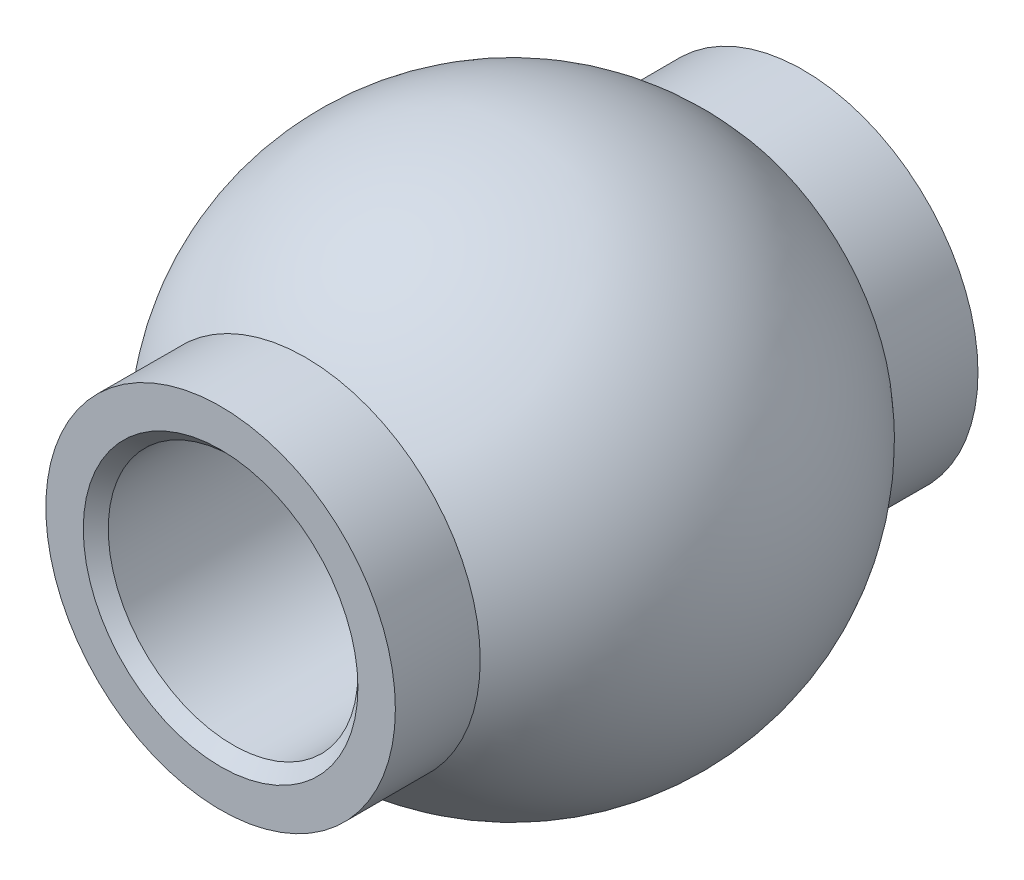
SolidWorks part; units mm, degrees
ref_plane "Front" through (0, 0, 0) normal (0, 0, 1) x (1, 0, 0)
ref_plane "Top" through (0, 0, 0) normal (0, 1, 0) x (1, 0, 0)
ref_plane "Right" through (0, 0, 0) normal (1, 0, 0) x (0, 0, -1)
sketch "Sketch1" plane through (0, 0, 0) normal (0, 0, 1) x (1, 0, 0)
  line L0 (0, 0) -> (0, -34.925)
  line L1 (0, -34.925) -> (4.7625, -34.925)
  line L2 (4.7625, -34.925) -> (4.7625, 0)
  line L3 (4.7625, 0) -> (0, 0)
  line L5 (0, 33.3375) -> (0, 0) construction
  line L6 (0, 33.3375) -> (14.2875, 33.3375) construction
  line L7 (14.2875, 33.3375) -> (14.2875, 19.05) construction
  line L8 (-4.7625, -34.925) -> (-4.7625, 0) construction
  line L9 (3.8092, -34.925) -> (4.7625, -33.9717)
  line L10 (4.8772, -34.8588) -> (4.8772, -35.918) construction
  line L11 (4.8772, -35.918) -> (3.9599, -35.3884) construction
  line L12 (3.9599, -35.3884) -> (4.8772, -34.8588) construction
  line L13 (3.9599, -35.3884) -> (4.0745, -35.3884) construction
  line L14 (4.8772, -35.3884) -> (4.7625, -35.3884) construction
  line L15 (4.0745, -35.4546) -> (4.0745, -35.3222) construction
  line L16 (4.7625, -35.8518) -> (4.7625, -34.925) construction
  line L17 (4.8198, -35.8849) -> (4.8198, -34.8919) construction
  arc A0 (8.5725, 7.62) -> (0, 33.3375) centre (0, 19.05) ccw construction
  circle A1 centre (0, 19.05) radius 4.7625 construction
  circle A2 centre (0, 19.05) radius 10.3187 construction
  circle A3 centre (0, 19.05) radius 10.8347 construction
  arc A4 (4.7625, 0) -> (8.5725, 7.62) centre (14.2875, 0) cw construction
  point P16 (-4.7625, -31.2179)
  point P28 (4.0745, -35.3884)
  point P31 (4.7625, -35.3884)
  point P34 (4.8198, -35.3884)
  dimension "Ball Dia" = 20.6375
  dimension "D1" = 21.6694
  dimension "ID" = 9.525
  dimension "D2" = 3.7071
  dimension "D3" = 45
  dimension "D4" = 0.9533
  dimension "Pitch" = 1.0592
  dimension "D5" = 0.1324
  dimension "Thread Size" = 9.525
  dimension "Overall Width" = 28.575
  dimension "Shank Thread Length" = 34.925
  dimension "Shank Center Length" = 53.975
sketch "Sketch2" plane through (0, 0, 0) normal (1, 0, 0) x (0, 0, -1)
  line L0 (-11.1125, 19.05) -> (11.1125, 19.05)
  line L2 (0, 25.7175) -> (0, 12.3825)
  line L3 (0, 23.8125) -> (0, 14.2875) construction
  line L4 (11.1125, 25.7175) -> (-11.1125, 25.7175)
  line L5 (11.1125, 23.8125) -> (-11.1125, 23.8125)
  line L6 (11.1125, 14.2875) -> (-11.1125, 14.2875)
  line L7 (11.1125, 12.3825) -> (-11.1125, 12.3825)
  line L8 (0, 19.05) -> (-11.1125, 24.8348) construction
  line L9 (0, 19.05) -> (-11.1125, 13.2652) construction
  point P0 (0, 23.8125)
  point P4 (0, 19.05)
  point P9 (0, 19.05)
  point P10 (0, 14.2875)
  point P18 (0, 23.8125)
  point P21 (0, 25.7175)
  point P24 (0, 14.2875)
  point P27 (0, 12.3825)
  dimension "D1" = 13.335
  dimension "Overall Thickness" = 22.225
  dimension "Maximum Ball Swivel" = 55
sketch "Sketch13" plane through (0, 0, 0) normal (0, 0, 1) x (1, 0, 0)
  line L0 (3.8092, -34.925) -> (4.7625, -33.9717) construction
  line L1 (3.8092, -34.925) -> (4.7625, -33.9717)
  line L4 (0, 0) -> (0, -34.925)
  line L5 (0, -34.925) -> (4.7625, -34.925)
  line L6 (4.7625, -34.925) -> (4.7625, 0)
  line L7 (4.7625, 0) -> (0, 0)
  line L8 (0, 0) -> (0, -34.925)
  line L9 (0, -34.925) -> (3.8092, -34.925)
  line L10 (4.7625, -33.9717) -> (4.7625, 0)
  line L11 (4.7625, 0) -> (0, 0)
  dimension "D1" = 0
revolve "Revolve4" [suppressed] add sketch "Sketch13" angle 360 about L8
sketch "Sketch4" plane through (0, 0, 0) normal (0, 0, 1) x (1, 0, 0)
  line L0 (4.7625, 0) -> (0, 0) construction
  line L1 (0, 8.7312) -> (0, 0)
  line L2 (0, 33.3375) -> (0, 0) construction
  line L3 (4.7625, 0) -> (0, 0)
  line L5 (0, 33.3375) -> (0, 29.3687)
  line L6 (0, 33.3375) -> (0, 35.8775) construction
  arc A0 (8.5725, 7.62) -> (0, 33.3375) centre (0, 19.05) ccw construction
  arc A1 (8.5725, 7.62) -> (0, 33.3375) centre (0, 19.05) ccw
  arc A2 (8.5725, 7.62) -> (4.7625, 0) centre (14.2875, 0) ccw construction
  arc A3 (8.5725, 7.62) -> (4.7625, 0) centre (14.2875, 0) ccw
  circle A4 centre (0, 19.05) radius 10.3187 construction
  arc A5 (0, 8.7312) -> (0, 29.3687) centre (0, 19.05) ccw
  dimension "D1" = 2.54
revolve "Revolve2" [suppressed] add sketch "Sketch4" angle 360 about L6
sketch "Sketch5" [suppressed] plane through (0, 0, 0) normal (1, 0, 0) x (0, 0, -1)
  line L0 (4.5641, 33.3375) -> (14.2875, 33.3375)
  line L1 (-4.5641, 33.3375) -> (4.5641, 33.3375) construction
  line L2 (-4.5641, 33.3375) -> (-4.5641, 1.8256)
  line L3 (-4.7625, 0) -> (4.7625, 0) construction
  line L4 (4.5641, 33.3375) -> (4.5641, 1.8256)
  line L5 (14.2875, 33.3375) -> (14.2875, 0)
  line L6 (14.2875, 0) -> (4.7625, 0)
  line L7 (-4.7625, 0) -> (-14.2875, 0)
  line L8 (-14.2875, 0) -> (-14.2875, 33.3375)
  line L9 (-14.2875, 33.3375) -> (-4.5641, 33.3375)
  line L10 (4.7625, 0) -> (4.5641, 1.8256)
  line L11 (-4.7625, 0) -> (-4.5641, 1.8256)
  line L12 (-4.5641, 1.8256) -> (4.5641, 1.8256) construction
  line L13 (0, 0) -> (0, 1.8256) construction
  arc A0 (8.5725, 7.62) -> (-8.5725, 7.62) centre (0, 19.05) ccw construction
  dimension "F" = 9.1281
  dimension "D2" = 1.8256
  dimension "D1" = 9.525
extrude "Cut-Extrude1" [suppressed] cut sketch "Sketch5" against normal through all and the other way through all
sketch "Sketch7" plane through (0, 0, 0) normal (0, 0, 1) x (1, 0, 0)
  line L0 (0, 29.3687) -> (0, 8.7312)
  line L1 (0, 33.3375) -> (0, 0) construction
  line L2 (0, 0) -> (0, 8.7312) construction
  arc A0 (0, 8.7312) -> (0, 29.3687) centre (0, 19.05) ccw
  circle A1 centre (0, 19.05) radius 10.3187 construction
revolve "Revolve3" add sketch "Sketch7" angle 360 about L2
sketch "Sketch10" plane through (0, 0, 0) normal (0, 0, 1) x (1, 0, 0)
  circle A0 centre (0, 19.05) radius 4.7625 construction
  circle A1 centre (0, 19.05) radius 4.7625
extrude "Cut-Extrude4" cut sketch "Sketch10" against normal through all and the other way through all
sketch "Sketch12" plane through (0, 0, 0) normal (0, 0, 1) x (1, 0, 0)
  circle A0 centre (0, 19.05) radius 6.6675
  circle A1 centre (0, 19.05) radius 4.7625 construction
  circle A2 centre (0, 19.05) radius 4.7625
  dimension "D1" = 13.335
extrude "Extrude1" add sketch "Sketch12" against normal up to vertex (11.1125 mm away) and the other way up to vertex (11.1125 mm away) up to point (0, 19.05, -11.1125) other way up to point (0, 19.05, 11.1125)
chamfer "Chamfer1" distance 0.4762 angle 45 2 edges at (4.7625, 19.05, -11.1125) (4.7625, 19.05, 11.1125)
sketch "Sketch11" [suppressed] plane through (0, 0, 0) normal (1, 0, 0) x (0, 0, -1)
  line L5 (0, 19.05) -> (0.0074, 19.05) construction
  line L9 (-4.5641, 32.5889) -> (-4.5641, 7.62) construction
  line L10 (4.5641, 7.62) -> (4.5641, 32.5889) construction
  arc A0 (-7.8753, 12.3825) -> (7.8753, 12.3825) centre (0, 19.05) ccw construction
  arc A1 (7.8753, 25.7175) -> (-7.8753, 25.7175) centre (0, 19.05) ccw construction
  arc A2 (-4.5641, 9.7955) -> (4.5641, 9.7955) centre (0, 19.05) ccw
  arc A3 (4.5641, 28.3045) -> (-4.5641, 28.3045) centre (0, 19.05) ccw
sketch "Sketch14" [suppressed] plane through (0, -34.925, 0) normal (0, -1, 0) x (1, 0, 0)
  circle A0 centre (0, 0) radius 4.7625
curve "Helix/Spiral1" [suppressed] pitch 1.0592 height 35.9842 turns 33.9736
split "Split1" [suppressed] bodies to split 122 118 115
sketch "Sketch15" plane through (0, 0, 0) normal (0, 0, 1) x (1, 0, 0)
  line L0 (4.0745, -35.3222) -> (4.8198, -34.8919)
  line L1 (4.8198, -34.8919) -> (4.8198, -35.8849)
  line L2 (4.8198, -35.8849) -> (4.0745, -35.4546)
  line L3 (4.0745, -35.4546) -> (4.0745, -35.3222)
sweep "Cut-Sweep1" [suppressed] cut profiles "Sketch15" path "Helix/Spiral1"
sketch "Sketch16" plane through (0, 0, 0) normal (0, 1, 0) x (1, 0, 0)
  circle A0 centre (0, 0) radius 4.7625
extrude "Boss-Extrude1" [suppressed] add sketch "Sketch16" against normal blind 2.54 draft 45
sketch "Sketch17" plane through (0, 0, 0) normal (0, 0, 1) x (1, 0, 0)
  point P1 (0, 19.05)
equation "\"D1@Sketch1\"=\"Ball Dia@Sketch1\"*1.05"
equation "\"D1@Chamfer1\" = \"ID@Sketch1\" / 20"
equation "\"D1@Sketch5\"= \"Thread Size@Sketch1\""
equation "\"D2@Sketch5\"=\"F@Sketch5\"/5"
equation "\"D1@Sketch12\"= \"ID@Sketch1\" * 1.4"
equation "\"D5@Sketch1\"=\"Pitch@Sketch1\"/8"
equation "\"D4@Sketch1\"=\"Pitch@Sketch1\"*.9"
equation "\"D3@Helix/Spiral1\"= \"Shank Thread Length@Sketch1\" + \"Pitch@Sketch1\""
equation "\"D4@Helix/Spiral1\"=\"Pitch@Sketch1\""
equation "\"D2@Sketch1\"=\"Pitch@Sketch1\"*3.5"
equation "\"D1@Sketch2\"=\"ID@Sketch1\"*1.4"
